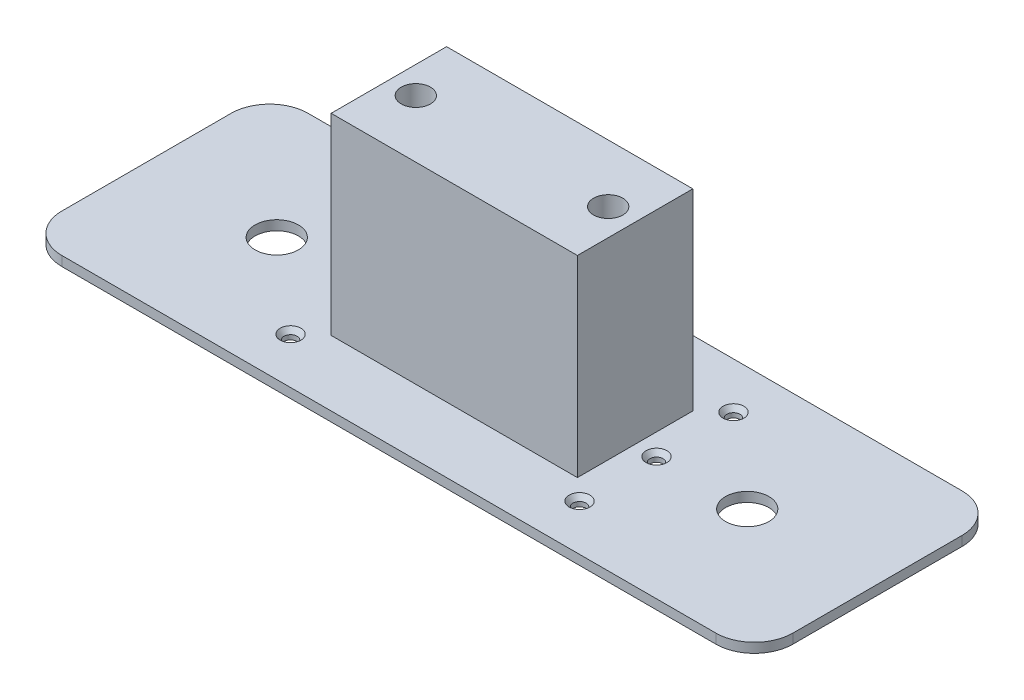
SolidWorks part; units mm, degrees
material "ABS"
ref_plane "Front" through (0, 0, 0) normal (0, 0, 1) x (1, 0, 0)
ref_plane "Top" through (0, 0, 0) normal (0, 1, 0) x (1, 0, 0)
ref_plane "Right" through (0, 0, 0) normal (1, 0, 0) x (0, 0, -1)
sketch "Sketch1" plane through (0, 0, 0) normal (0, 1, 0) x (1, 0, 0)
  line L1 (-60.325, 20.32) -> (60.325, 20.32)
  line L2 (-60.325, 20.32) -> (-60.325, -20.32)
  line L3 (-60.325, -20.32) -> (60.325, -20.32)
  line L4 (60.325, 20.32) -> (60.325, -20.32)
  line L5 (-60.325, 20.32) -> (60.325, -20.32) construction
  line L6 (-60.325, -20.32) -> (60.325, 20.32) construction
  point P0 (0, 0)
  dimension "D1" = 120.65
  dimension "D2" = 40.64
extrude "Boss-Extrude1" add sketch "Sketch1" along normal blind 1.5875
fillet "Fillet1" radius 6.35 4 edges at (-60.325, 0.7937, 20.32) (-60.325, 0.7937, -20.32) (60.325, 0.7937, -20.32) (60.325, 0.7937, 20.32)
sketch "Sketch2" plane through (0, 1.5875, 0) normal (0, 1, 0) x (1, 0, 0)
  line L1 (-20.32, 9.525) -> (20.32, 9.525)
  line L2 (-20.32, 9.525) -> (-20.32, -9.525)
  line L3 (-20.32, -9.525) -> (20.32, -9.525)
  line L4 (20.32, 9.525) -> (20.32, -9.525)
  line L5 (-20.32, 9.525) -> (20.32, -9.525) construction
  line L6 (-20.32, -9.525) -> (20.32, 9.525) construction
  point P0 (0, 0)
  dimension "D1" = 40.64
  dimension "D2" = 19.05
extrude "Boss-Extrude2" add sketch "Sketch2" along normal blind 31.75
sketch "Sketch3" plane through (0, 33.3375, 0) normal (0, 1, 0) x (1, 0, 0)
  line L0 (-15.875, 0) -> (15.875, 0) construction
  point P4 (0, 0)
  point P6 (-15.875, 0)
  point P7 (15.875, 0)
  dimension "D1" = 31.75
hole_wizard "#10 Clearance Hole1" positions "Sketch4" profile "Sketch5" hole size "#10" standard "ANSI Inch"
sketch "Sketch4" plane through (0, 33.3375, 0) normal (0, 1, 0) x (1, 0, 0)
  point P0 (-15.875, 0)
  point P3 (15.875, 0)
sketch "Sketch5" plane through (-15.875, 33.3375, 0) normal (1, 0, 0) x (0, 0, 1)
  line L0 (0, 0) -> (0, 26.8499)
  line L1 (0, 26.8499) -> (2.413, 25.4)
  line L2 (2.413, 25.4) -> (2.413, 0)
  line L5 (2.413, 0) -> (0, 0)
  line L10 (0, 26.8499) -> (-2.413, 25.4) construction
  line L11 (0, -6.35) -> (0, 107.95) construction
  dimension "Hole Dia." = 4.826
  dimension "Hole Depth" = 25.4
  dimension "Drill Angle" = 118
sketch "Sketch10" plane through (0, 0, 0) normal (0, -1, 0) x (1, 0, 0)
  line L1 (0, -50) -> (0, 50) construction
  circle A0 centre (23.85, -12.7) radius 1.0795 construction
  circle A1 centre (23.85, 12.7) radius 1.0795 construction
  circle A2 centre (23.85, 0) radius 1.0795 construction
  point P0 (23.85, 12.7)
  point P1 (23.85, 0)
  point P2 (23.85, -12.7)
  point P18 (-23.85, -12.7)
  point P19 (-23.85, 0)
  point P20 (-23.85, 12.7)
hole_wizard "#2 Clearance Hole1" positions "Sketch11" profile "Sketch12" hole size "#2" standard "ANSI Inch" end condition through all
sketch "Sketch11" plane through (0, 1.5875, 0) normal (0, 1, 0) x (1, 0, 0)
  point P0 (-23.85, 12.7)
  point P3 (-23.85, 0)
  point P6 (-23.85, -12.7)
  point P9 (23.85, -12.7)
  point P12 (23.85, 0)
  point P15 (23.85, 12.7)
sketch "Sketch12" plane through (-23.85, 1.5875, -12.7) normal (1, 0, 0) x (0, 0, 1)
  line L0 (0, 0) -> (0, 1.5875)
  line L1 (0, 1.5875) -> (1.0795, 1.5875)
  line L2 (1.0795, 1.5875) -> (1.0795, 0.8275)
  line L3 (1.0795, 0.8275) -> (1.7145, 0)
  line L5 (1.7145, 0) -> (0, 0)
  line L6 (-1.0795, 0.8275) -> (-1.7145, 0) construction
  line L11 (0, -6.35) -> (0, 107.95) construction
  dimension "Thru Hole Dia." = 2.159
  dimension "Thru Hole Depth" = 1.5875
  dimension "Near C'Sink Dia." = 3.429
  dimension "Near C'Sink Angle" = 75
sketch "Sketch13" plane through (0, 0, 0) normal (0, -1, 0) x (-1, 0, 0)
  line L0 (0, 50) -> (0, -50) construction
  circle A1 centre (38.825, 0) radius 3.575
  circle A3 centre (-38.825, 0) radius 3.575
  arc A4 (35.95, 1.9961) -> (35.95, -1.9961) centre (38.825, 0) ccw construction
  dimension "D1" = 7.15
extrude "Cut-Extrude1" cut sketch "Sketch13" against normal through all
